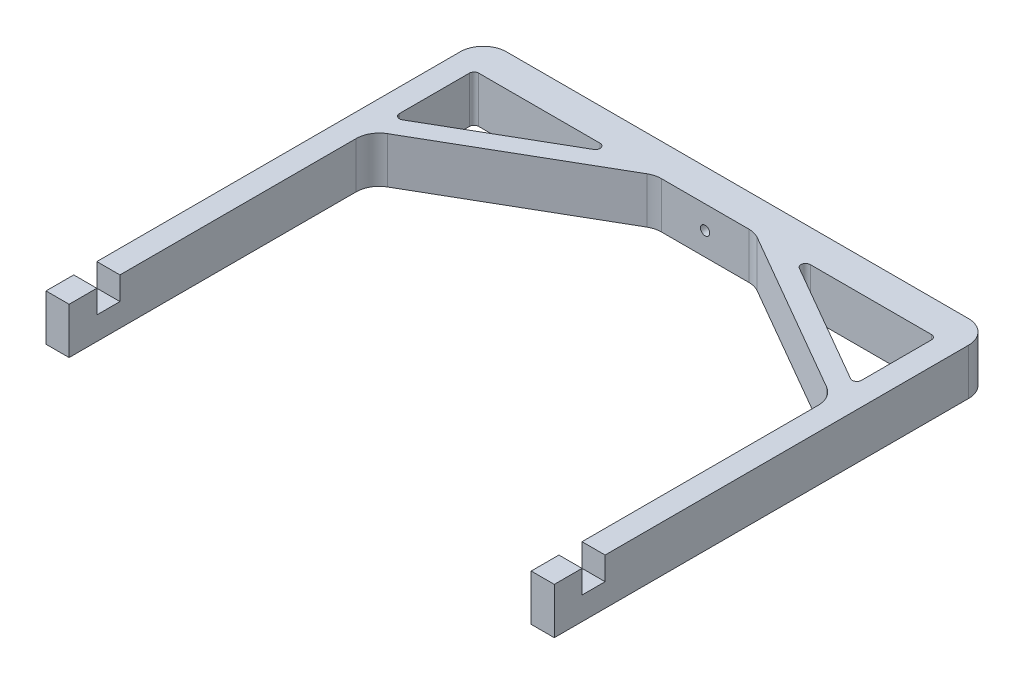
SolidWorks part; units mm, degrees
ref_plane "Płaszczyzna przednia" through (0, 0, 0) normal (0, 0, 1) x (1, 0, 0)
ref_plane "Płaszczyzna górna" through (0, 0, 0) normal (0, 1, 0) x (1, 0, 0)
ref_plane "Płaszczyzna prawa" through (0, 0, 0) normal (1, 0, 0) x (0, 0, -1)
sketch "Szkic1" plane through (0, 0, 0) normal (0, 1, 0) x (1, 0, 0)
  line L0 (0, 0) -> (0, 94.6385) construction
  line L1 (50, 94.6385) -> (-50, 94.6385)
  line L2 (-55, 89.6385) -> (-55, 0)
  line L3 (-55, 0) -> (-50, 0)
  line L4 (-50, 71.4867) -> (-50, 86.6385)
  line L5 (-49, 87.6385) -> (-22.7564, 87.6385)
  line L6 (-48.5, 70.6207) -> (-22.2564, 85.7724)
  line L7 (-47.5, 66.4434) -> (-11.9493, 86.9686)
  line L8 (-55, 6) -> (-50, 6)
  line L9 (-55, 11) -> (-50, 11)
  line L10 (-50, 62.1132) -> (-50, 0)
  line L11 (-9.4493, 87.6385) -> (9.4493, 87.6385)
  line L12 (50, 62.1132) -> (50, 0)
  line L13 (55, 11) -> (50, 11)
  line L14 (55, 6) -> (50, 6)
  line L15 (47.5, 66.4434) -> (11.9493, 86.9686)
  line L16 (48.5, 70.6207) -> (22.2564, 85.7724)
  line L17 (49, 87.6385) -> (22.7564, 87.6385)
  line L18 (50, 71.4867) -> (50, 86.6385)
  line L19 (55, 0) -> (50, 0)
  line L20 (55, 89.6385) -> (55, 0)
  arc A0 (-50, 86.6385) -> (-49, 87.6385) centre (-49, 86.6385) cw
  arc A1 (-22.7564, 87.6385) -> (-22.2564, 85.7724) centre (-22.7564, 86.6385) cw
  arc A2 (-50, 71.4867) -> (-48.5, 70.6207) centre (-49, 71.4867) ccw
  arc A3 (50, 71.4867) -> (48.5, 70.6207) centre (49, 71.4867) cw
  arc A4 (22.7564, 87.6385) -> (22.2564, 85.7724) centre (22.7564, 86.6385) ccw
  arc A5 (50, 86.6385) -> (49, 87.6385) centre (49, 86.6385) ccw
  arc A6 (-50, 94.6385) -> (-55, 89.6385) centre (-50, 89.6385) ccw
  arc A7 (55, 89.6385) -> (50, 94.6385) centre (50, 89.6385) ccw
  arc A8 (50, 62.1132) -> (47.5, 66.4434) centre (45, 62.1132) ccw
  arc A9 (-47.5, 66.4434) -> (-50, 62.1132) centre (-45, 62.1132) ccw
  arc A10 (11.9493, 86.9686) -> (9.4493, 87.6385) centre (9.4493, 82.6385) ccw
  arc A11 (-11.9493, 86.9686) -> (-9.4493, 87.6385) centre (-9.4493, 82.6385) cw
  point P2 (-52.5, 6)
  point P24 (0, 87.6385)
  point P42 (-55, 94.6385)
  point P43 (-57.9702, 24.7568)
  point P44 (-65.0554, 43.922)
  point P47 (55, 94.6385)
  point P50 (50, 65)
  point P53 (-50, 65)
  point P56 (10.789, 87.6385)
  point P59 (-10.789, 87.6385)
  point P61 (-52.5, 0)
  dimension "D1" = 5
  dimension "D2" = 5
  dimension "D3" = 50
  dimension "D4" = 94.6385
  dimension "D5" = 62.1132
  dimension "D6" = 6
  dimension "D7" = 11
  dimension "D8" = 5
extrude "Dodanie-wyciągnięcie1" add sketch "Szkic1" along normal blind 10 contours L11 L0 L1 L2 L9 L10 L7 A2 L4 A0 L5 A1 L6 | L0 L11 L15 L12 L13 L20 L1 A5 L18 A3 L16 A4 L17 | L20 L14 L12 L19 | L10 L8 L2 L3 region at (-4.7246, 0, -88.6395) region at (1.001, 0, -91.1385) region at (52.5, 0, -3) region at (-52.5, 0, -3)
extrude "Dodanie-wyciągnięcie2" add sketch "Szkic1<3>" along normal blind 5 contours L10 L9 L2 L8 | L20 L13 L12 L14 region at (52.5, 0, -8.5) region at (-52.5, 0, -8.5)
sketch "Szkic1<3>" plane through (0, 0, 0) normal (0, 1, 0) x (1, 0, 0) same geometry as "Szkic1"
sketch "Szkic2" plane through (0, 0, -87.6385) normal (0, 0, 1) x (1, 0, 0)
  line L0 (0, 0) -> (0, 10) construction
  line L1 (-9.4493, 10) -> (9.4493, 10) construction
  circle A0 centre (0, 5) radius 1
extrude "Wytnij-wyciągnięcie1" cut sketch "Szkic2" against normal through all
